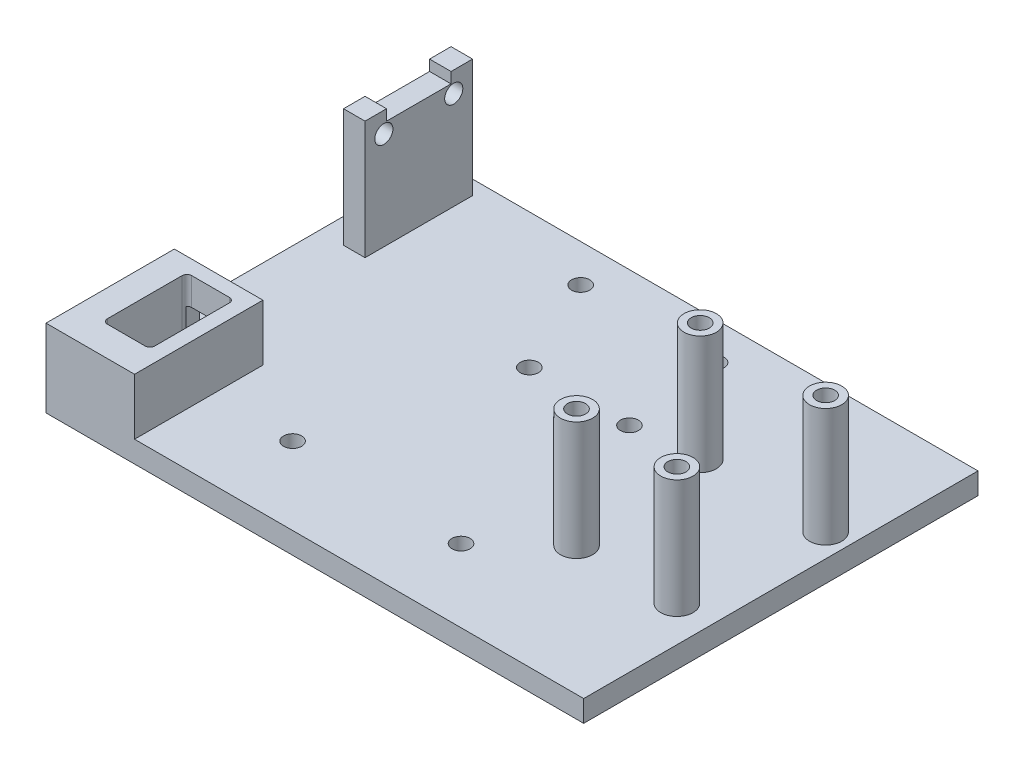
SolidWorks part; units mm, degrees
ref_plane "Front Plane" through (0, 0, 0) normal (0, 0, 1) x (1, 0, 0)
ref_plane "Top Plane" through (0, 0, 0) normal (0, 1, 0) x (1, 0, 0)
ref_plane "Right Plane" through (0, 0, 0) normal (1, 0, 0) x (0, 0, -1)
sketch "Sketch1" plane through (0, 0, 0) normal (0, 1, 0) x (1, 0, 0)
  line L1 (0, 0) -> (150, 0)
  line L2 (0, 0) -> (0, 110)
  line L3 (0, 110) -> (150, 110)
  line L4 (150, 0) -> (150, 110)
  dimension "D1" = 150
  dimension "D2" = 110
extrude "Boss-Extrude1" add sketch "Sketch1" along normal blind 6
hole_wizard "#8 (0.199) Diameter Hole1" positions "Sketch2" profile "Sketch3" hole size "#8" standard "ANSI Inch" end condition up to next
sketch "Sketch2" plane through (0, 6, 0) normal (0, 1, 0) x (1, 0, 0)
  point P0 (90.38, 72.39)
  point P3 (62.44, 72.39)
  point P6 (47.2, 21.59)
  point P9 (95.46, 20.32)
  point P24 (49.66, 99.5)
  point P27 (87.16, 99.5)
  point P30 (0, 0)
  point P31 (0, 0)
  point P32 (0, 0)
  point P33 (0, 0)
sketch "Sketch3" plane through (90.38, 6, -72.39) normal (1, 0, 0) x (0, 0, 1)
  line L0 (0, 0) -> (0, 6)
  line L1 (0, 6) -> (2.5273, 6)
  line L2 (2.5273, 6) -> (2.5273, 0)
  line L5 (2.5273, 0) -> (0, 0)
  line L11 (0, -6.35) -> (0, 107.95) construction
  dimension "Thru Hole Dia." = 5.0546
  dimension "Thru Hole Depth" = 6
sketch "Sketch4" plane through (0, 6, 0) normal (0, 1, 0) x (1, 0, 0)
  line L0 (150, 110) -> (0, 110) construction
  line L1 (7, 106) -> (13, 106)
  line L2 (7, 106) -> (7, 76)
  line L3 (7, 76) -> (13, 76)
  line L4 (13, 106) -> (13, 76)
  line L5 (0, 110) -> (0, 0) construction
  dimension "D1" = 30
  dimension "D2" = 6
  dimension "D3" = 4
  dimension "D4" = 7
extrude "Boss-Extrude2" add sketch "Sketch4" along normal blind 30
ref_plane "Plane1" through (0, 0, -91) normal (0, 0, -1) x (-1, 0, 0)
hole_wizard "#8 (0.199) Diameter Hole2" positions "Sketch5" profile "Sketch6" hole size "#8" standard "ANSI Inch" end condition up to next
sketch "Sketch5" plane through (7, 0, 0) normal (-1, 0, 0) x (0, 0, 1)
  point P0 (-81.25, 33.27)
  point P3 (-100.75, 33.27)
sketch "Sketch6" plane through (7, 33.27, -81.25) normal (0, 1, 0) x (0, 0, 1)
  line L0 (0, 0) -> (0, 6)
  line L1 (0, 6) -> (2.5273, 6)
  line L2 (2.5273, 6) -> (2.5273, 0)
  line L5 (2.5273, 0) -> (0, 0)
  line L11 (0, -6.35) -> (0, 107.95) construction
  dimension "Thru Hole Dia." = 5.0546
  dimension "Thru Hole Depth" = 6
sketch "Sketch7" plane through (0, 36, 0) normal (0, 1, 0) x (1, 0, 0)
  line L0 (13, 76) -> (13, 106) construction
  line L1 (7, 106) -> (13, 106)
  line L2 (7, 106) -> (7, 100)
  line L3 (7, 100) -> (13, 100)
  line L4 (13, 106) -> (13, 100)
  line L6 (7, 76) -> (13, 76)
  line L7 (7, 76) -> (7, 82)
  line L8 (7, 82) -> (13, 82)
  line L9 (13, 76) -> (13, 82)
  dimension "D1" = 6
  dimension "D2" = 6
extrude "Boss-Extrude3" add sketch "Sketch7" along normal blind 3
sketch "Sketch9" plane through (0, 6, 0) normal (0, 1, 0) x (1, 0, 0)
  line L0 (20.2, 9.65) -> (20.2, 30.45) construction
  line L1 (8.85, 8.8) -> (19.35, 8.8) construction
  line L2 (8, 30.45) -> (8, 9.65) construction
  line L3 (19.35, 31.3) -> (8.85, 31.3) construction
  line L4 (20.2, 9.65) -> (20.2, 30.45) construction
  line L5 (8.85, 8.8) -> (19.35, 8.8) construction
  line L6 (8, 30.45) -> (8, 9.65) construction
  line L7 (19.35, 31.3) -> (8.85, 31.3) construction
  line L8 (20.7, 9.65) -> (20.7, 30.45)
  line L9 (19.35, 31.8) -> (8.85, 31.8)
  line L10 (7.5, 30.45) -> (7.5, 9.65)
  line L11 (8.85, 8.3) -> (19.35, 8.3)
  line L13 (0, 0) -> (24.7, 0)
  line L14 (0, 0) -> (0, 35.8)
  line L15 (0, 35.8) -> (24.7, 35.8)
  line L16 (24.7, 0) -> (24.7, 35.8)
  arc A0 (20.2, 30.45) -> (19.35, 31.3) centre (19.35, 30.45) ccw construction
  arc A1 (19.35, 8.8) -> (20.2, 9.65) centre (19.35, 9.65) ccw construction
  arc A2 (8, 9.65) -> (8.85, 8.8) centre (8.85, 9.65) ccw construction
  arc A3 (8.85, 31.3) -> (8, 30.45) centre (8.85, 30.45) ccw construction
  arc A4 (20.2, 30.45) -> (19.35, 31.3) centre (19.35, 30.45) ccw construction
  arc A5 (19.35, 8.8) -> (20.2, 9.65) centre (19.35, 9.65) ccw construction
  arc A6 (8, 9.65) -> (8.85, 8.8) centre (8.85, 9.65) ccw construction
  arc A7 (8.85, 31.3) -> (8, 30.45) centre (8.85, 30.45) ccw construction
  arc A8 (20.7, 30.45) -> (19.35, 31.8) centre (19.35, 30.45) ccw
  arc A9 (8.85, 31.8) -> (7.5, 30.45) centre (8.85, 30.45) ccw
  arc A10 (7.5, 9.65) -> (8.85, 8.3) centre (8.85, 9.65) ccw
  arc A11 (19.35, 8.3) -> (20.7, 9.65) centre (19.35, 9.65) ccw
  dimension "D2" = 4
  dimension "D3" = 4
  dimension "D1" = 0.5
extrude "Boss-Extrude4" add sketch "Sketch9" along normal blind 15.7
sketch "Sketch10" plane through (0, 0, -35.8) normal (0, 0, -1) x (-1, 0, 0)
  line L0 (-7, 39) -> (-7, 6) construction
  line L1 (-20.7, 6) -> (-7, 6)
  line L2 (-20.7, 6) -> (-20.7, 14)
  line L3 (-20.7, 14) -> (-7, 14)
  line L4 (-7, 6) -> (-7, 14)
  dimension "D1" = 8
extrude "Cut-Extrude1" cut sketch "Sketch10" against normal up to surface (4.5 mm away)
sketch "Sketch11" plane through (0, 6, 0) normal (0, 1, 0) x (1, 0, 0)
  arc A0 (113.25, 36) -> (110.75, 36) centre (112, 36) ccw construction
  arc A1 (141.25, 36) -> (138.75, 36) centre (140, 36) ccw construction
  arc A2 (144.75, 74) -> (142.25, 74) centre (143.5, 74) ccw construction
  arc A3 (109.75, 74) -> (107.25, 74) centre (108.5, 74) ccw construction
  arc A4 (113.25, 36) -> (110.75, 36) centre (112, 36) ccw construction
  arc A5 (141.25, 36) -> (138.75, 36) centre (140, 36) ccw construction
  arc A6 (144.75, 74) -> (142.25, 74) centre (143.5, 74) ccw construction
  arc A7 (109.75, 74) -> (107.25, 74) centre (108.5, 74) ccw construction
  circle A8 centre (108.5, 74) radius 4.5
  circle A9 centre (143.5, 74) radius 4.5
  circle A10 centre (112, 36) radius 4.5
  circle A11 centre (140, 36) radius 4.5
  dimension "D1" = 9
extrude "Boss-Extrude5" add sketch "Sketch11" along normal blind 33
hole_wizard "#8 (0.199) Diameter Hole3" positions "Sketch12" profile "Sketch13" hole size "#8" standard "ANSI Inch" end condition up to next
sketch "Sketch12" plane through (0, 39, 0) normal (0, 1, 0) x (1, 0, 0)
  point P0 (108.5, 74)
  point P3 (143.5, 74)
  point P6 (112, 36)
  point P9 (140, 36)
sketch "Sketch13" plane through (108.5, 39, -74) normal (1, 0, 0) x (0, 0, 1)
  line L0 (0, 0) -> (0, 39)
  line L1 (0, 39) -> (2.5273, 39)
  line L2 (2.5273, 39) -> (2.5273, 0)
  line L5 (2.5273, 0) -> (0, 0)
  line L11 (0, -6.35) -> (0, 107.95) construction
  dimension "Thru Hole Dia." = 5.0546
  dimension "Thru Hole Depth" = 39
